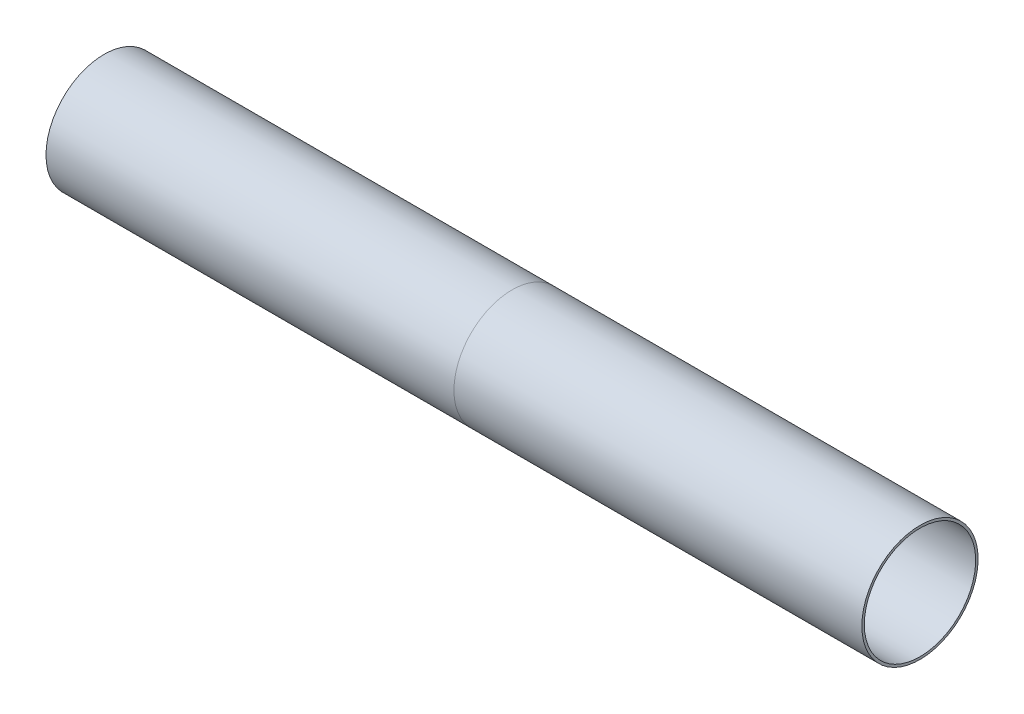
SolidWorks part; units mm, degrees
other "Coupler"
other "Middle Bit"
other "End Part"
ref_plane "Front Plane" through (0, 0, 0) normal (0, 0, 1) x (1, 0, 0)
ref_plane "Top Plane" through (0, 0, 0) normal (0, 1, 0) x (1, 0, 0)
ref_plane "Right Plane" through (0, 0, 0) normal (1, 0, 0) x (0, 0, -1)
sketch "Sketch2" plane through (0, 0, 0) normal (0, 1, 0) x (1, 0, 0)
  line L0 (0, 0) -> (200, 0)
  line L1 (200, 27.3) -> (200, 0) construction
  line L2 (0, 27.3) -> (0, 0) construction
  line L3 (200, 28.5) -> (0, 28.5)
  line L4 (200, 28.5) -> (200, 27.3)
  line L5 (200, 27.3) -> (0, 27.3)
  line L6 (0, 28.5) -> (0, 27.3)
  line L7 (100, 27.3) -> (100, 28.5) construction
  line L8 (200, 27.9) -> (0, 27.9) construction
  line L9 (0, 27.3) -> (11.4301, 26.3)
  line L10 (11.4301, 26.3) -> (12.4301, 27.3)
  line L11 (11.4301, 26.3) -> (11.4301, 27.3) construction
  line L12 (-12.4301, 27.3) -> (12.4301, 27.3)
  line L13 (0, 27.3) -> (-11.4301, 26.3)
  line L14 (-11.4301, 26.3) -> (-12.4301, 27.3)
  line L15 (-200, 27.3) -> (0, 27.3)
  line L16 (-200, 28.5) -> (0, 28.5)
  line L17 (-200, 28.5) -> (-200, 27.3)
  line L18 (-100, 28.5) -> (-100, 0) construction
  line L19 (-187.5699, 27.3) -> (-200, 27.3)
  line L20 (-188.5699, 26.3) -> (-187.5699, 27.3)
  line L21 (-200, 27.3) -> (-188.5699, 26.3)
  point P328 (100, 27.9)
  dimension "D1" = 200
  dimension "D2" = 27.3
  dimension "D3" = 1.2
  dimension "D4" = 45
  dimension "D5" = 5
  dimension "D6" = 1
revolve "Revolve1" add sketch "Sketch2" angle 360 about L0 region at (100, 0, -27.9) region at (7.9534, 0, -26.9667)
revolve "Revolve2" add sketch "Sketch2<3>" angle 360 about L0 region at (-100, 0, -27.9) region at (-7.9534, 0, -26.9667)
sketch "Sketch2<3>" plane through (0, 0, 0) normal (0, 1, 0) x (1, 0, 0) same geometry as "Sketch2"
sketch "Sketch3" plane through (0, 0, 0) normal (0, 1, 0) x (1, 0, 0)
  line L0 (-11.4301, 26.3) -> (0, 27.3)
  line L1 (0, 27.3) -> (11.4301, 26.3)
  line L2 (11.4301, 26.3) -> (11.4301, 25.1)
  line L3 (11.4301, 25.1) -> (-11.4301, 25.1)
  line L4 (-11.4301, 25.1) -> (-11.4301, 26.3)
  point P4 (-11.4301, 25.5)
  dimension "D1" = 1.2
revolve "Revolve3" add sketch "Sketch3" angle 360 about L0
